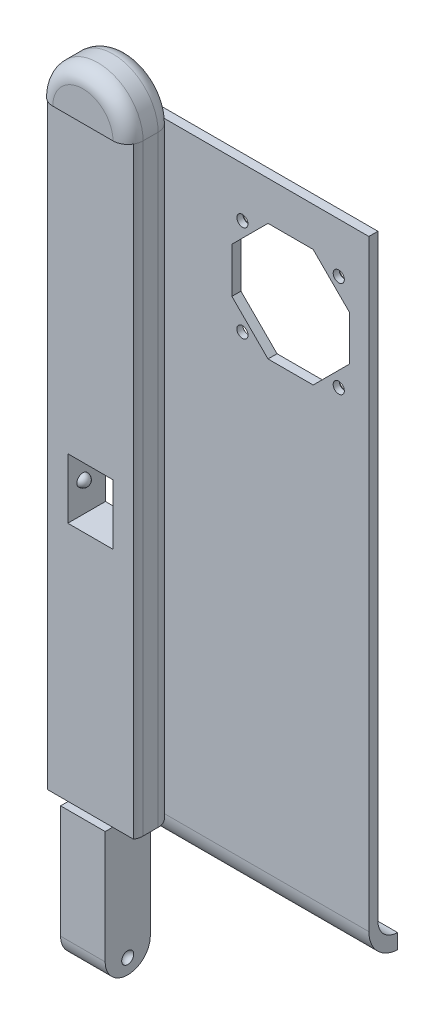
SolidWorks part; units mm, degrees
ref_plane "Front Plane" through (0, 0, 0) normal (0, 0, 1) x (1, 0, 0)
ref_plane "Top Plane" through (0, 0, 0) normal (0, 1, 0) x (1, 0, 0)
ref_plane "Right Plane" through (0, 0, 0) normal (1, 0, 0) x (0, 0, -1)
sketch "Sketch1" plane through (0, 0, 0) normal (0, 0, 1) x (1, 0, 0)
  line L0 (-7.4, -150) -> (7.4, -150)
  line L1 (7.4, -150) -> (7.4, -100)
  line L2 (7.4, -100) -> (15, -100)
  line L3 (15, -100) -> (15, 100)
  line L4 (-15, 100) -> (-15, -100)
  line L5 (-15, -100) -> (-7.4, -100)
  line L6 (-7.4, -100) -> (-7.4, -150)
  arc A0 (15, 100) -> (-15, 100) centre (0, 100) ccw
  point P7 (-15, 0)
  dimension "D2" = 14.8
  dimension "D3" = 15
  dimension "D1" = 250
  dimension "D4" = 15
  dimension "D5" = 50
extrude "Boss-Extrude1" add sketch "Sketch1" along normal mid plane 15
fillet "Fillet1" radius 5 8 edges at (15, 0, -7.5) (0, 115, -7.5) (15, 0, 7.5) (0, 115, 7.5) (-7.4, -150, 0) (7.4, -150, 0) (-15, 0, -7.5) (-15, 0, 7.5)
sketch "Sketch2" plane through (0, 0, 0) normal (0, 0, 1) x (1, 0, 0)
  line L0 (-23.2914, -140) -> (24.3018, -140) construction
  line L1 (-15, -100) -> (-10, -100) construction
  line L3 (-7.4, -100) -> (-7.4, -145) construction
  line L4 (-7.4, -138) -> (-7.4, -140)
  line L6 (7.4, -145) -> (7.4, -100) construction
  line L7 (7.4, -138) -> (7.4, -140)
  line L8 (-7.4, -140) -> (-5.4, -140)
  line L9 (7.4, -140) -> (5.4, -140)
  arc A2 (-5.4, -140) -> (-7.4, -138) centre (-7.4, -140) ccw
  arc A3 (5.4, -140) -> (7.4, -138) centre (7.4, -140) cw
  dimension "D1" = 40
  dimension "D2" = 2
  dimension "D3" = 2
sketch "Sketch3" plane through (0, 0, 0) normal (1, 0, 0) x (0, 0, -1)
  line L0 (7.5, -100) -> (7.5, 100) construction
  line L5 (17, -109.9875) -> (17, -104.9875)
  line L6 (10.5, -98.4875) -> (10.5, 100)
  line L7 (10.5, 100) -> (7.5, 100)
  line L8 (7.5, -100) -> (7.5, 100)
  arc A0 (7.5, -100) -> (17, -109.9875) centre (17.5, -100) ccw
  arc A1 (17, -104.9875) -> (10.5, -98.4875) centre (17, -98.4875) cw
  dimension "D1" = 10
  dimension "D4" = 6.5
  dimension "D2" = 3
  dimension "D3" = 5
sketch "Sketch4" plane through (0, 0, 7.5) normal (0, 0, 1) x (1, 0, 0)
  line L0 (-10, 100) -> (-10, -100) construction
  line L1 (-7.5, 0) -> (7.5, 0)
  line L2 (-7.5, 0) -> (-7.5, -20)
  line L3 (-7.5, -20) -> (7.5, -20)
  line L4 (7.5, 0) -> (7.5, -20)
  line L5 (-15, 100) -> (-10, 100) construction
  dimension "D1" = 20
  dimension "D2" = 15
  dimension "D3" = 2.5
extrude "Cut-Extrude1" cut sketch "Sketch4" against normal through all
sketch "Sketch5" plane through (0, 0, 0) normal (0, 0, 1) x (1, 0, 0)
  line L0 (-21.9659, -10) -> (20.5009, -10) construction
  line L1 (7.5, 0) -> (-7.5, 0) construction
  line L2 (-7.5, -10) -> (-5.5, -10)
  line L3 (-7.5, 0) -> (-7.5, -20) construction
  line L4 (-7.5, -8) -> (-7.5, -10)
  line L5 (7.5, -10) -> (5.5, -10)
  line L6 (7.5, -20) -> (7.5, 0) construction
  line L7 (7.5, -8) -> (7.5, -10)
  arc A0 (-5.5, -10) -> (-7.5, -8) centre (-7.5, -10) ccw
  arc A1 (5.5, -10) -> (7.5, -8) centre (7.5, -10) cw
  dimension "D1" = 10
  dimension "D2" = 2
  dimension "D3" = 2
revolve "Revolve2" add sketch "Sketch5" angle 360 about L0
revolve "Cut-Revolve1" cut sketch "Sketch2" angle 360 about L0
sketch "Sketch6" plane through (-7.4, 0, 0) normal (-1, 0, 0) x (0, 0, 1)
  line L0 (-7.5, -100) -> (-7.5, -145) construction
  line L1 (7.5, -100) -> (7.5, -145) construction
  line L2 (-7.5, -137.5) -> (-7.5, -150)
  line L3 (-7.5, -150) -> (7.5, -150)
  line L4 (7.5, -150) -> (-7.5, -150) construction
  line L5 (7.5, -150) -> (7.5, -137.5)
  line L6 (-7.5, -145) -> (7.5, -145) construction
  arc A0 (-7.5, -137.5) -> (7.5, -137.5) centre (0, -137.5) ccw
extrude "Cut-Extrude2" cut sketch "Sketch6" against normal through all
extrude "Boss-Extrude2" add sketch "Sketch3" along normal blind 80
sketch "Sketch7" plane through (0, 0, 0) normal (-1, 0, 0) x (0, 0, 1)
  line L0 (-10.5, 100) -> (-7.5, 100) construction
  line L1 (-7.5, 100) -> (-7.5, 0) construction
  line L2 (-7.5, 0) -> (-7.5, -20) construction
  line L3 (-7.5, -20) -> (-7.5, -100) construction
  line L4 (-17, -109.9875) -> (-17, -104.9875) construction
  line L5 (-10.5, -98.4875) -> (-10.5, 100) construction
  line L6 (-10.5, 100) -> (-7.5, 100)
  line L7 (-7.5, 100) -> (-7.5, 0)
  line L8 (-7.5, 0) -> (-7.5, -20)
  line L9 (-7.5, -20) -> (-7.5, -100)
  line L10 (-17, -109.9875) -> (-17, -104.9875)
  line L11 (-10.5, -98.4875) -> (-10.5, 100)
  arc A0 (-17, -109.9875) -> (-7.5, -100) centre (-17.5, -100) ccw construction
  arc A1 (-17, -104.9875) -> (-10.5, -98.4875) centre (-17, -98.4875) ccw construction
  arc A2 (-17, -109.9875) -> (-7.5, -100) centre (-17.5, -100) ccw
  arc A3 (-17, -104.9875) -> (-10.5, -98.4875) centre (-17, -98.4875) ccw
extrude "Boss-Extrude3" add sketch "Sketch7" along normal blind 5
sketch "Sketch9" plane through (0, 0, -10.5) normal (0, 0, -1) x (-1, 0, 0)
  line L0 (-7.5, -20) -> (-7.5, 0) construction
  line L1 (-7.5, -20) -> (-7.5, 0)
  line L2 (-7.5, 0) -> (5, 0) construction
  line L3 (5, -20) -> (-7.5, -20) construction
  line L4 (-7.5, 0) -> (5, 0)
  line L5 (5, -20) -> (-7.5, -20)
  line L6 (5, -20) -> (5, 0)
extrude "Cut-Extrude3" cut sketch "Sketch9" against normal blind 3
sketch "Sketch10" plane through (-15, 0, 0) normal (-1, 0, 0) x (0, 0, 1)
  line L0 (7.5, -100) -> (5, -100)
  line L1 (2.5, -100) -> (7.5, -100) construction
  line L2 (5, -100) -> (5, 100)
  line L3 (2.5, 100) -> (7.5, 100) construction
  line L4 (5, 100) -> (7.5, 100)
  line L5 (7.5, 100) -> (7.5, 110) construction
  line L6 (7.5, 100) -> (7.5, -100)
extrude "Cut-Extrude4" cut sketch "Sketch10" against normal through all
sketch "Sketch11" plane through (0, 0, -10.5) normal (0, 0, -1) x (-1, 0, 0)
  line L0 (-80, -98.4875) -> (5, -98.4875) construction
  line L1 (-46.5, 87.0125) -> (-61.5, 87.0125)
  line L2 (-61.5, 87.0125) -> (-73.5, 75.0125)
  line L3 (-73.5, 75.0125) -> (-73.5, 60.0125)
  line L4 (-73.5, 60.0125) -> (-61.5, 48.0125)
  line L5 (-61.5, 48.0125) -> (-46.5, 48.0125)
  line L6 (-46.5, 48.0125) -> (-34.5, 60.0125)
  line L7 (-34.5, 60.0125) -> (-34.5, 75.0125)
  line L8 (-34.5, 75.0125) -> (-46.5, 87.0125)
  line L9 (-80, -98.4875) -> (-80, 100) construction
  circle A1 centre (-38, 83.5125) radius 1.85
  circle A2 centre (-38, 51.5125) radius 1.85
  circle A3 centre (-70, 83.5125) radius 1.85
  circle A4 centre (-70, 51.5125) radius 1.85
  point P12 (-73.5, 67.5125)
  point P21 (-54, 87.0125)
  dimension "D1" = 32
  dimension "D8" = 3.7
  dimension "D9" = 16
  dimension "D2" = 32
  dimension "D3" = 32
  dimension "D4" = 150
  dimension "D5" = 39
  dimension "D6" = 15
  dimension "D7" = 39
  dimension "D10" = 10
  dimension "D11" = 16
extrude "Cut-Extrude5" cut sketch "Sketch11" against normal through all
sketch "Sketch12" plane through (0, 0, -10.5) normal (0, 0, -1) x (-1, 0, 0)
  circle A0 centre (-38, 83.5125) radius 3
  circle A1 centre (-70, 83.5125) radius 3
  circle A2 centre (-70, 51.5125) radius 3
  circle A3 centre (-38, 51.5125) radius 3.25
  dimension "D1" = 6
  dimension "D2" = 6
  dimension "D3" = 6
  dimension "D4" = 6.5
extrude "Cut-Extrude6" cut sketch "Sketch12" against normal blind 1
